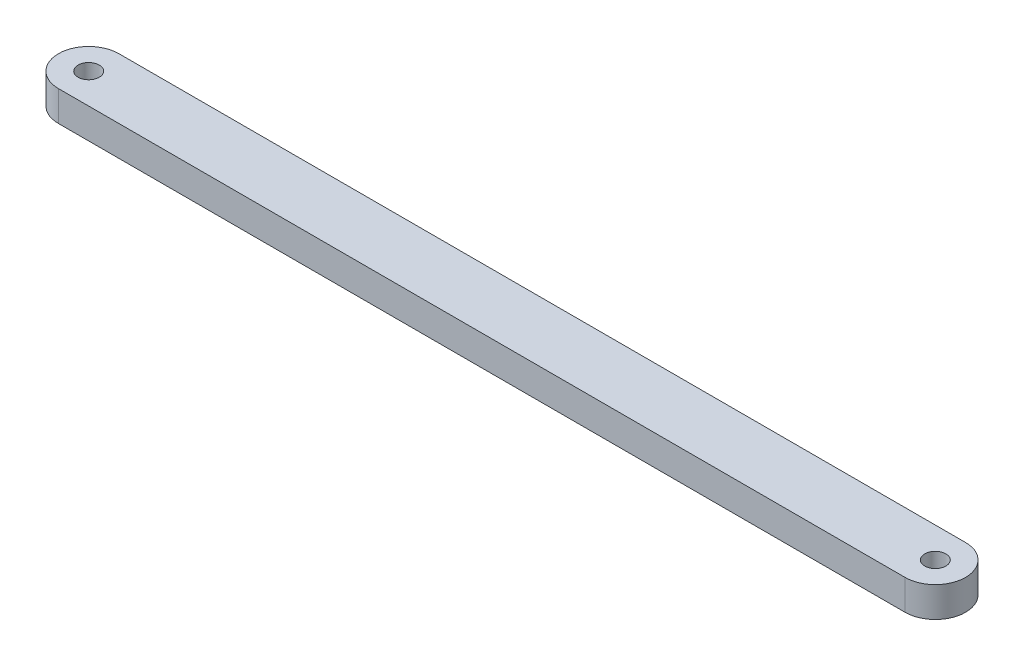
SolidWorks part; units mm, degrees
ref_plane "Front Plane" through (0, 0, 0) normal (0, 0, 1) x (1, 0, 0)
ref_plane "Top Plane" through (0, 0, 0) normal (0, 1, 0) x (1, 0, 0)
ref_plane "Right Plane" through (0, 0, 0) normal (1, 0, 0) x (0, 0, -1)
sketch "Sketch1" plane through (0, 0, 0) normal (0, 1, 0) x (1, 0, 0)
  line L0 (-140, 0) -> (140, 0) construction
  line L1 (-140, 10) -> (140, 10)
  line L2 (-140, -10) -> (140, -10)
  arc A0 (-140, 10) -> (-140, -10) centre (-140, 0) ccw
  arc A1 (140, -10) -> (140, 10) centre (140, 0) ccw
  circle A2 centre (-140, 0) radius 3.5
  circle A3 centre (140, 0) radius 3.5
  point P2 (0, 0)
  dimension "D3" = 7
  dimension "D4" = 7
  dimension "D1" = 280
  dimension "D2" = 20
extrude "Boss-Extrude1" add sketch "Sketch1" along normal blind 10
equation "\"D4@Sketch1\"=\"D3@Sketch1\""
